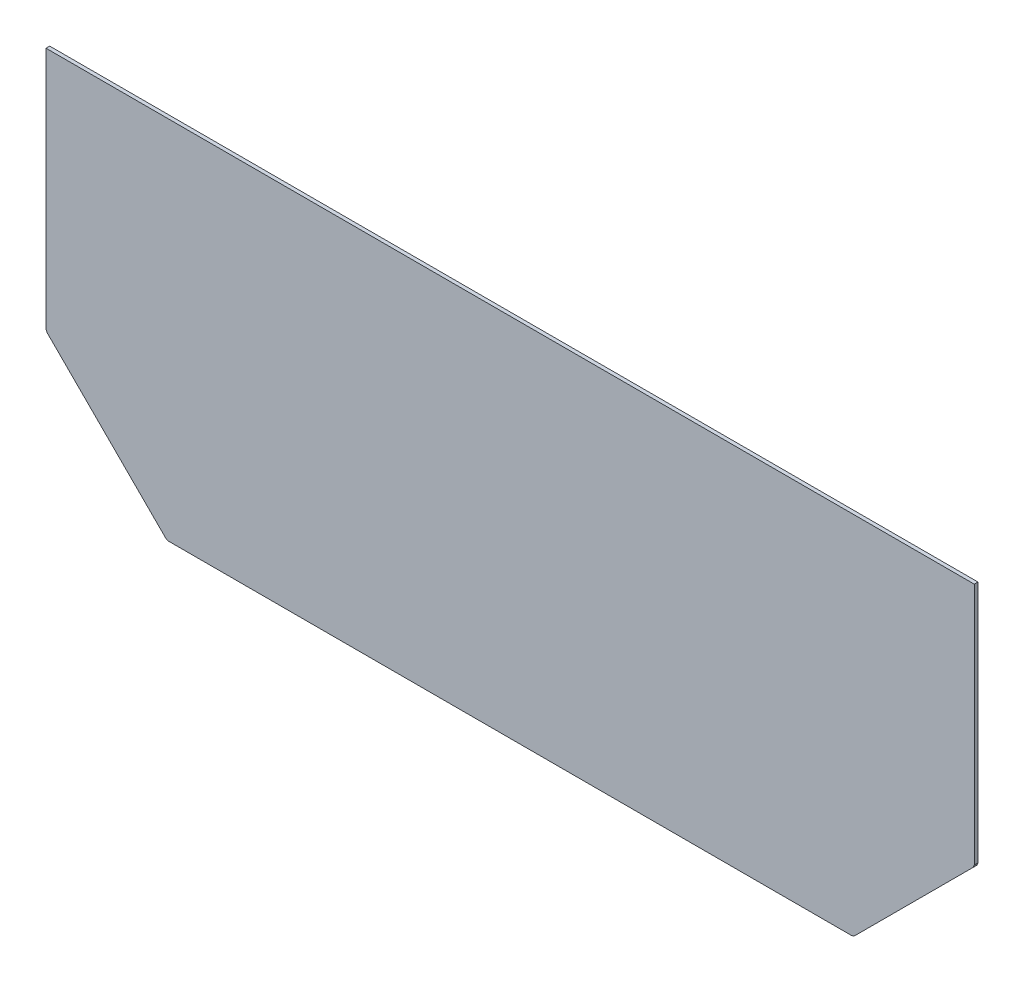
SolidWorks part; units mm, degrees
ref_plane "Ön Düzlem" through (0, 0, 0) normal (0, 0, 1) x (1, 0, 0)
ref_plane "Üst Düzlem" through (0, 0, 0) normal (0, 1, 0) x (1, 0, 0)
ref_plane "Sağ Düzlem" through (0, 0, 0) normal (1, 0, 0) x (0, 0, -1)
sketch "Çizim1" plane through (0, 0, 0) normal (0, 0, 1) x (1, 0, 0)
  line L0 (-685.0909, -304.1105) -> (424.968, -304.1105)
  line L1 (-685.0909, -304.1105) -> (-689.3336, -302.3531)
  line L2 (-689.3336, -302.3531) -> (-882.3041, -109.3826)
  line L3 (-882.3041, -109.3826) -> (-884.0615, -105.1399)
  line L4 (-884.0615, -105.1399) -> (-884.0615, 289.8895)
  line L5 (-884.0615, 289.8895) -> (623.9385, 289.8895)
  line L6 (-130.0615, 289.8895) -> (-130.0615, -304.1105) construction
  line L7 (623.9385, -105.1399) -> (623.9385, 289.8895)
  line L8 (622.1812, -109.3826) -> (623.9385, -105.1399)
  line L9 (429.2106, -302.3531) -> (622.1812, -109.3826)
  line L10 (424.968, -304.1105) -> (429.2106, -302.3531)
  dimension "D1" = 1508
  dimension "D2" = 594
base flange "Taban-Flanş1" sketch "Çizim1" thickness 6 reverse thickness direction no parameters "D1"=6
sketch "Büküm-Çizgileri1" [suppressed] plane through (0, 0, 0) normal (0, 1, 0) x (1, 0, 0)
sketch "Sınırlandırma-Kutusu1" [suppressed] plane through (0, 0, 0) normal (0, 1, 0) x (1, 0, 0)
sheet metal parameters "Sac-Levha1" thickness 6 parameters "D1"=6
flat pattern "Düz-Çoğaltma1" [suppressed]
sketch "Büküm-Çizgileri2" plane through (0, 0, 0) normal (0, 1, 0) x (1, 0, 0)
sketch3d "Sınırlandırma-Kutusu2" [suppressed]
  line L0 (-884.0615, -304.1105, 0) -> (623.9385, -304.1105, 0) construction
  line L1 (-884.0615, 289.8895, 0) -> (623.9385, 289.8895, 0) construction
  line L2 (-884.0615, -304.1105, 0) -> (-884.0615, 289.8895, 0) construction
  line L3 (623.9385, -304.1105, 0) -> (623.9385, 289.8895, 0) construction
